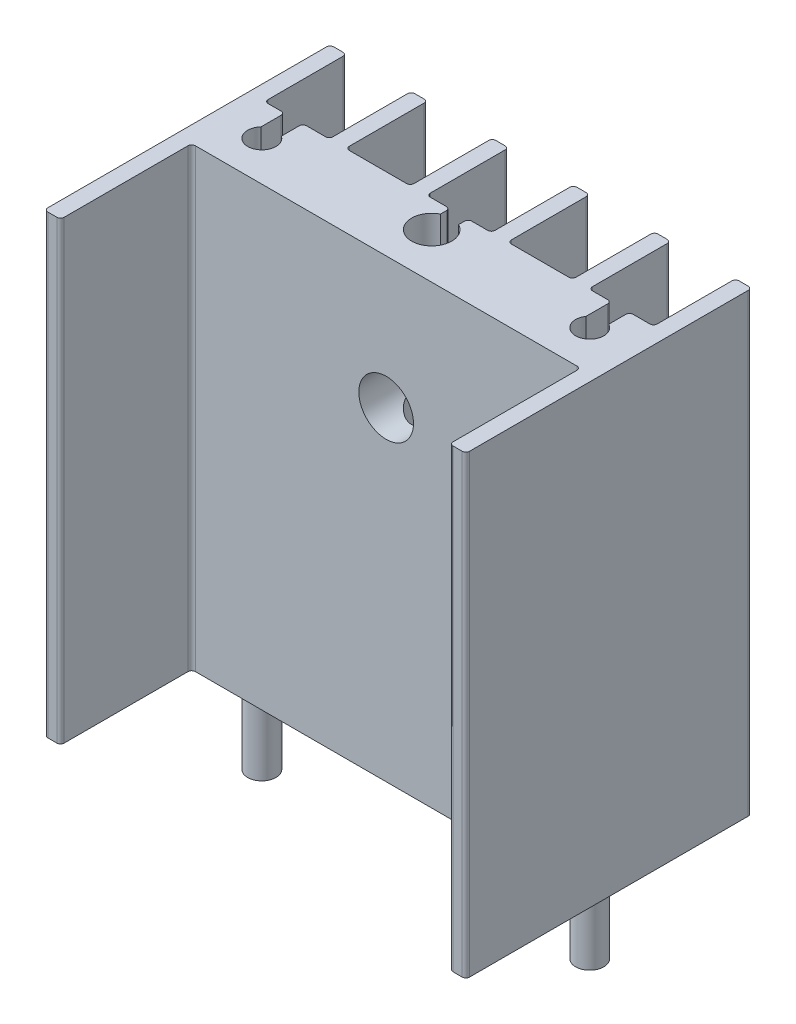
SolidWorks part; units mm, degrees
ref_plane "前视基准面" through (0, 0, 0) normal (0, 0, 1) x (1, 0, 0)
ref_plane "上视基准面" through (0, 0, 0) normal (0, 1, 0) x (1, 0, 0)
ref_plane "右视基准面" through (0, 0, 0) normal (1, 0, 0) x (0, 0, -1)
sketch "草图1" plane through (0, 0, 0) normal (0, 1, 0) x (1, 0, 0)
  line L0 (-11.375, -7.85) -> (-10.875, -7.85)
  line L1 (-11.575, -7.85) -> (11.575, -7.85) construction
  line L2 (-11.575, -7.65) -> (-11.575, 7.65)
  line L3 (-11.575, 7.85) -> (11.575, 7.85) construction
  line L4 (11.575, -7.65) -> (11.575, 7.65)
  line L5 (-11.575, -7.85) -> (11.575, 7.85) construction
  line L6 (-11.575, 7.85) -> (11.575, -7.85) construction
  line L7 (-10.675, -7.65) -> (-10.675, -0.65)
  line L8 (11.375, -7.85) -> (10.875, -7.85)
  line L9 (10.675, -7.65) -> (10.675, -0.65)
  line L10 (10.675, -0.65) -> (-10.675, -0.65)
  line L11 (-11.375, 7.85) -> (-10.875, 7.85)
  line L12 (-10.675, 7.65) -> (-10.675, 3.55)
  line L13 (-10.475, 3.35) -> (-9.7702, 3.35)
  line L14 (11.375, 7.85) -> (10.875, 7.85)
  line L15 (10.675, 7.65) -> (10.675, 3.55)
  line L16 (10.475, 3.35) -> (9.5581, 3.35)
  line L17 (7.125, 3.55) -> (7.125, 7.65)
  line L18 (6.925, 7.85) -> (6.425, 7.85)
  line L19 (-7.125, 3.55) -> (-7.125, 7.65)
  line L20 (-6.925, 7.85) -> (-6.425, 7.85)
  line L21 (-7.125, 3.35) -> (7.125, 3.35) construction
  line L22 (-6.225, 7.65) -> (-6.225, 3.55)
  line L23 (6.225, 7.65) -> (6.225, 3.55)
  line L24 (6.025, 3.35) -> (2.875, 3.35)
  line L25 (-6.025, 3.35) -> (-2.875, 3.35)
  line L26 (-2.675, 3.55) -> (-2.675, 7.65)
  line L27 (-2.475, 7.85) -> (-1.975, 7.85)
  line L28 (2.675, 3.55) -> (2.675, 7.65)
  line L29 (2.475, 7.85) -> (1.975, 7.85)
  line L30 (-1.775, 7.65) -> (-1.775, 3.55)
  line L31 (-1.575, 3.35) -> (-0.7, 3.35)
  line L32 (1.775, 3.55) -> (1.775, 7.65)
  line L33 (0, -0.65) -> (0, 1.85) construction
  line L34 (0, 7.85) -> (0, -7.85) construction
  line L36 (-0.5, 3.15) -> (-0.5, 2.8298)
  line L37 (0.5, 3.15) -> (0.5, 2.8298)
  line L38 (0.7, 3.35) -> (1.575, 3.35)
  line L40 (-9.5702, 3.15) -> (-9.5702, 2.0499)
  line L41 (-8.5702, 3.15) -> (-8.5702, 2.1699)
  line L42 (-8.3702, 3.35) -> (-7.325, 3.35)
  line L43 (8.1581, 3.35) -> (7.325, 3.35)
  line L44 (8.3581, 3.15) -> (8.3581, 1.9593)
  line L45 (9.3581, 3.15) -> (9.3581, 2.2123)
  arc A0 (-0.5, 2.8298) -> (0.5, 2.8298) centre (0, 1.85) ccw
  arc A1 (8.3581, 1.9593) -> (9.3581, 2.2123) centre (9, 1.525) ccw
  arc A2 (-8.5702, 2.1699) -> (-9.5702, 2.0499) centre (-9, 1.525) cw
  arc A3 (-10.675, 3.55) -> (-10.475, 3.35) centre (-10.475, 3.55) ccw
  arc A4 (-7.325, 3.35) -> (-7.125, 3.55) centre (-7.325, 3.55) ccw
  arc A5 (-6.225, 3.55) -> (-6.025, 3.35) centre (-6.025, 3.55) ccw
  arc A6 (-2.875, 3.35) -> (-2.675, 3.55) centre (-2.875, 3.55) ccw
  arc A7 (-1.775, 3.55) -> (-1.575, 3.35) centre (-1.575, 3.55) ccw
  arc A8 (1.575, 3.35) -> (1.775, 3.55) centre (1.575, 3.55) ccw
  arc A9 (2.875, 3.35) -> (2.675, 3.55) centre (2.875, 3.55) cw
  arc A10 (6.225, 3.55) -> (6.025, 3.35) centre (6.025, 3.55) cw
  arc A11 (7.325, 3.35) -> (7.125, 3.55) centre (7.325, 3.55) cw
  arc A12 (10.675, 3.55) -> (10.475, 3.35) centre (10.475, 3.55) cw
  arc A13 (9.3581, 3.15) -> (9.5581, 3.35) centre (9.5581, 3.15) cw
  arc A14 (8.3581, 3.15) -> (8.1581, 3.35) centre (8.1581, 3.15) ccw
  arc A15 (-9.7702, 3.35) -> (-9.5702, 3.15) centre (-9.7702, 3.15) cw
  arc A16 (-8.3702, 3.35) -> (-8.5702, 3.15) centre (-8.3702, 3.15) ccw
  arc A17 (-0.7, 3.35) -> (-0.5, 3.15) centre (-0.7, 3.15) cw
  arc A18 (0.7, 3.35) -> (0.5, 3.15) centre (0.7, 3.15) ccw
  arc A19 (-11.375, -7.85) -> (-11.575, -7.65) centre (-11.375, -7.65) cw
  arc A20 (-10.875, -7.85) -> (-10.675, -7.65) centre (-10.875, -7.65) ccw
  arc A21 (10.875, -7.85) -> (10.675, -7.65) centre (10.875, -7.65) cw
  arc A22 (11.375, -7.85) -> (11.575, -7.65) centre (11.375, -7.65) ccw
  arc A23 (11.375, 7.85) -> (11.575, 7.65) centre (11.375, 7.65) cw
  arc A24 (10.875, 7.85) -> (10.675, 7.65) centre (10.875, 7.65) ccw
  arc A25 (7.125, 7.65) -> (6.925, 7.85) centre (6.925, 7.65) ccw
  arc A26 (6.425, 7.85) -> (6.225, 7.65) centre (6.425, 7.65) ccw
  arc A27 (2.675, 7.65) -> (2.475, 7.85) centre (2.475, 7.65) ccw
  arc A28 (1.975, 7.85) -> (1.775, 7.65) centre (1.975, 7.65) ccw
  arc A29 (-1.975, 7.85) -> (-1.775, 7.65) centre (-1.975, 7.65) cw
  arc A30 (-2.675, 7.65) -> (-2.475, 7.85) centre (-2.475, 7.65) cw
  arc A31 (-6.425, 7.85) -> (-6.225, 7.65) centre (-6.425, 7.65) cw
  arc A32 (-7.125, 7.65) -> (-6.925, 7.85) centre (-6.925, 7.65) cw
  arc A33 (-10.875, 7.85) -> (-10.675, 7.65) centre (-10.875, 7.65) cw
  arc A34 (-11.575, 7.65) -> (-11.375, 7.85) centre (-11.375, 7.65) cw
  point P0 (0, 0)
  point P33 (9, 1.525)
  point P43 (0, 3.35)
  point P47 (-9.0702, 3.35)
  point P51 (8.8581, 3.35)
  point P54 (-10.675, 3.35)
  point P60 (-6.225, 3.35)
  point P63 (-2.675, 3.35)
  point P66 (-1.775, 3.35)
  point P69 (1.775, 3.35)
  point P72 (2.675, 3.35)
  point P75 (6.225, 3.35)
  point P81 (10.675, 3.35)
  point P84 (9.3581, 3.35)
  point P87 (8.3581, 3.35)
  point P90 (-9.5702, 3.35)
  point P93 (-8.5702, 3.35)
  point P96 (-0.5, 3.35)
  point P99 (0.5, 3.35)
  point P105 (-10.675, -7.85)
  point P108 (10.675, -7.85)
  point P117 (10.675, 7.85)
  point P120 (7.125, 7.85)
  point P123 (6.225, 7.85)
  point P126 (2.675, 7.85)
  point P129 (1.775, 7.85)
  point P132 (-1.775, 7.85)
  point P135 (-2.675, 7.85)
  point P138 (-6.225, 7.85)
  point P141 (-7.125, 7.85)
  point P144 (-10.675, 7.85)
  dimension "D16" = 2.575
  dimension "D18" = 1.55
  dimension "D22" = 0.2
  dimension "D1" = 23.15
  dimension "D2" = 15.7
  dimension "D3" = 0.9
  dimension "D4" = 7.2
  dimension "D5" = 0.9
  dimension "D6" = 4
  dimension "D7" = 3.55
  dimension "D8" = 3.55
  dimension "D9" = 0.9
  dimension "D10" = 0.9
  dimension "D11" = 3.55
  dimension "D12" = 3.55
  dimension "D13" = 0.9
  dimension "D14" = 0.9
  dimension "D15" = 2.5
  dimension "D17" = 2.175
  dimension "D19" = 1
  dimension "D20" = 1
  dimension "D21" = 1
extrude "凸台-拉伸1" add sketch "草图1" along normal blind 25 contours L20 A31 L22 A5 L25 A6 L26 A30 L27 A29 L30 A7 L31 A17 L36 A0 L37 A18 L38 A8 L32 A28 L29 A27 L28 A9 L24 A10 L23 A26 L18 A25 L17 A11 L43 A14 L44 A1 L45 A13 L16 A12 L15 A24 L14 A23 L4 A22 L8 A21 L9 L10 L7 A20 L0 A19 L2 A34 L11 A33 L12 A3 L13 A15 L40 A2 L41 A16 L42 A4 L19 A32
sketch "草图2" plane through (0, 0, 0) normal (0, -1, 0) x (1, 0, 0)
  circle A0 centre (-9, -1.525) radius 0.775
  circle A1 centre (9, -1.525) radius 0.775
extrude "凸台-拉伸2" add sketch "草图2" along normal blind 5 and the other way blind 20 contours A1 | A0 region at (9, 0, -1.525)
fillet "圆角1" radius 0.2 2 edges at (10.675, 12.5, 0.65) (-10.675, 12.5, 0.65)
sketch "草图3" plane through (0, 0, 0.65) normal (0, 0, 1) x (1, 0, 0)
  line L0 (0, 0) -> (0, 25) construction
  line L1 (10.475, 25) -> (-10.475, 25) construction
  circle A0 centre (0, 17.78) radius 1.5
  dimension "D1" = 3
  dimension "D2" = 17.78
extrude "切除-拉伸1" cut sketch "草图3" against normal blind 10
